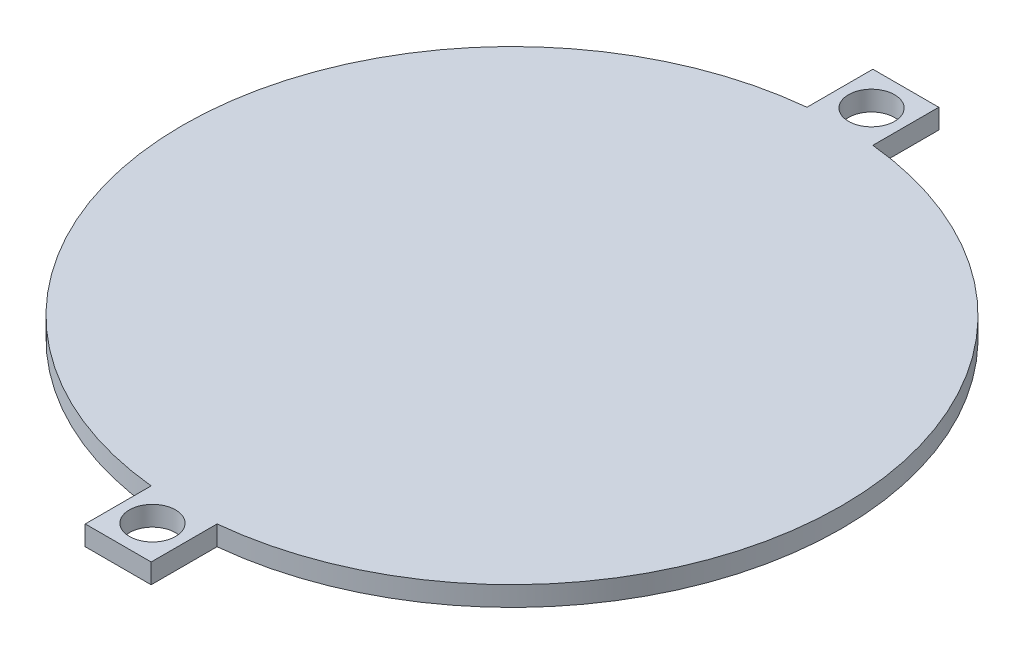
SolidWorks part; units mm, degrees
ref_plane "Front Plane" through (0, 0, 0) normal (0, 0, 1) x (1, 0, 0)
ref_plane "Top Plane" through (0, 0, 0) normal (0, 1, 0) x (1, 0, 0)
ref_plane "Right Plane" through (0, 0, 0) normal (1, 0, 0) x (0, 0, -1)
sketch "Sketch2" plane through (0, 0, 0) normal (0, 1, 0) x (1, 0, 0)
  circle A0 centre (0, 0) radius 50
  dimension "D1" = 100
extrude "Boss-Extrude1" add sketch "Sketch2" along normal blind 12
sketch "Sketch3" plane through (0, 0, 0) normal (0, -1, 0) x (1, 0, 0)
  line L1 (49.7494, -5) -> (59.7494, -5)
  line L2 (49.7494, -5) -> (49.7494, 5)
  line L3 (49.7494, 5) -> (59.7494, 5)
  line L4 (59.7494, -5) -> (59.7494, 5)
  line L5 (-59.7494, -5) -> (-49.7494, -5)
  line L6 (-59.7494, -5) -> (-59.7494, 5)
  line L7 (-59.7494, 5) -> (-49.7494, 5)
  line L8 (-49.7494, -5) -> (-49.7494, 5)
  circle A0 centre (0, 0) radius 48
  circle A1 centre (0, 0) radius 50 construction
  circle A2 centre (0, 0) radius 50 construction
  dimension "D1" = 96
  dimension "D2" = 10
  dimension "D3" = 10
  dimension "D4" = 10
  dimension "D5" = 10
extrude "Cut-Extrude1" cut sketch "Sketch3" against normal blind 10 contours A0
sketch "Sketch7" plane through (0, 0, 0) normal (0, -1, 0) x (-1, 0, 0)
  line L1 (-5, 49.7494) -> (5, 49.7494)
  line L2 (-5, 49.7494) -> (-5, 59.7494)
  line L3 (-5, 59.7494) -> (5, 59.7494)
  line L4 (5, 49.7494) -> (5, 59.7494)
  circle A0 centre (0, 0) radius 50 construction
  dimension "D1" = 10
  dimension "D2" = 10
extrude "Boss-Extrude12" add sketch "Sketch7" against normal blind 3 contours L2 L1 L4 L3
sketch "Sketch8" plane through (0, 0, 0) normal (0, -1, 0) x (-1, 0, 0)
  line L1 (-5, -59.7494) -> (5, -59.7494)
  line L2 (-5, -59.7494) -> (-5, -49.7494)
  line L3 (-5, -49.7494) -> (5, -49.7494)
  line L4 (5, -59.7494) -> (5, -49.7494)
  arc A0 (-5, 49.7494) -> (5, 49.7494) centre (0, 0) ccw construction
  dimension "D1" = 10
  dimension "10" = 10
extrude "Boss-Extrude13" add sketch "Sketch8" against normal blind 3
sketch "Sketch9" plane through (0, 0, 0) normal (0, -1, 0) x (1, 0, 0)
  line L0 (5, 59.7494) -> (-5, 59.7494) construction
  circle A0 centre (0, 54.5494) radius 3.5
  dimension "D1" = 7
  dimension "D2" = 5.2
extrude "Cut-Extrude2" cut sketch "Sketch9" against normal blind 10
sketch "Sketch10" plane through (0, 0, 0) normal (0, -1, 0) x (1, 0, 0)
  line L0 (5, -59.7494) -> (-5, -59.7494) construction
  circle A0 centre (0, -54.5494) radius 3.5
  dimension "D1" = 7
  dimension "D2" = 5.2
extrude "Cut-Extrude3" cut sketch "Sketch10" against normal blind 10
sketch "Sketch11" plane through (5, 0, 0) normal (1, 0, 0) x (0, 0, -1)
  line L1 (-59.7494, 3) -> (66.1312, 3)
  line L2 (-59.7494, 3) -> (-59.7494, 18.914)
  line L3 (-59.7494, 18.914) -> (66.1312, 18.914)
  line L4 (66.1312, 3) -> (66.1312, 18.914)
extrude "Cut-Extrude4" cut sketch "Sketch11" against normal blind 100 and the other way blind 100
sketch "Sketch12" plane through (0, 3, 0) normal (0, 1, 0) x (1, 0, 0)
  circle A0 centre (0, 0) radius 48
extrude "Boss-Extrude15" add sketch "Sketch12" against normal blind 3
